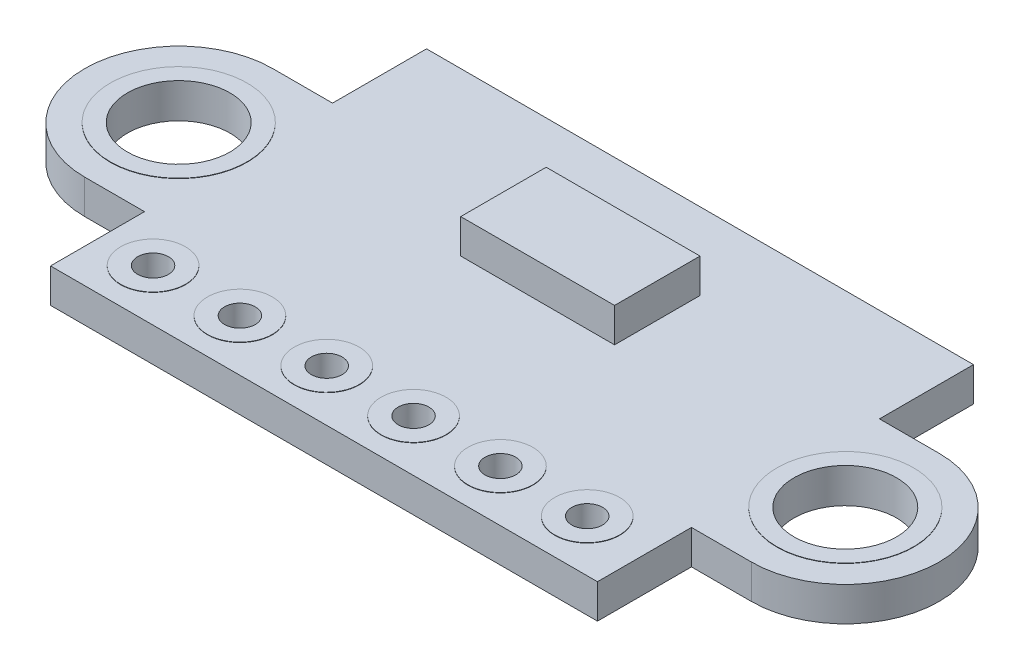
SolidWorks part; units mm, degrees
ref_plane "Front" through (0, 0, 0) normal (0, 0, 1) x (1, 0, 0)
ref_plane "Top" through (0, 0, 0) normal (0, 1, 0) x (1, 0, 0)
ref_plane "Right" through (0, 0, 0) normal (1, 0, 0) x (0, 0, -1)
sketch "Эскиз1" plane through (0, 0, 0) normal (0, 1, 0) x (1, 0, 0)
  line L0 (-38.6022, 0) -> (38.6022, 0) construction
  line L1 (8, -5.5) -> (-8, -5.5)
  line L2 (8, -5.5) -> (8, 5.5) construction
  line L3 (8, 5.5) -> (-8, 5.5)
  line L4 (-8, -5.5) -> (-8, 5.5) construction
  line L5 (8, -5.5) -> (-8, 5.5) construction
  line L6 (8, 5.5) -> (-8, -5.5) construction
  line L7 (-8, 5.5) -> (-8, 2.75)
  line L8 (0, -16.638) -> (0, 16.638) construction
  line L9 (-9.75, 2.75) -> (-8, 2.75)
  line L10 (-8, -5.5) -> (-8, -2.75)
  line L11 (-9.75, -2.75) -> (-8, -2.75)
  line L12 (9.75, -2.75) -> (8, -2.75)
  line L13 (8, -5.5) -> (8, -2.75)
  line L14 (8, 5.5) -> (8, 2.75)
  line L15 (9.75, 2.75) -> (8, 2.75)
  circle A0 centre (-9.75, 0) radius 1.5
  arc A1 (-9.75, 2.75) -> (-9.75, -2.75) centre (-9.75, 0) ccw
  circle A2 centre (9.75, 0) radius 1.5
  arc A3 (9.75, 2.75) -> (9.75, -2.75) centre (9.75, 0) cw
  circle A4 centre (-9.75, 0) radius 2
  circle A5 centre (9.75, 0) radius 2
  circle A6 centre (-6.5, -4) radius 0.45
  circle A7 centre (-6.5, -4) radius 0.95
  circle A8 centre (-3.96, -4) radius 0.95
  circle A9 centre (-3.96, -4) radius 0.45
  circle A10 centre (-1.42, -4) radius 0.95
  circle A11 centre (-1.42, -4) radius 0.45
  circle A12 centre (1.12, -4) radius 0.95
  circle A13 centre (1.12, -4) radius 0.45
  circle A14 centre (3.66, -4) radius 0.95
  circle A15 centre (3.66, -4) radius 0.45
  circle A16 centre (6.2, -4) radius 0.95
  circle A17 centre (6.2, -4) radius 0.45
  point P0 (0, 0)
  point P9 (0, 0)
  point P13 (0, 0)
  point P18 (-12.5, 0)
  point P25 (12.5, 0)
  dimension "D1" = 3
  dimension "D2" = 2.75
  dimension "D6" = 4
  dimension "D7" = 0.9
  dimension "D8" = 1.9
  dimension "D3" = 16
  dimension "D4" = 11
  dimension "D5" = 25
  dimension "D9" = 1.5
  dimension "D10" = 1.5
  dimension "D12" = 2.54
  dimension "D11" = 6
extrude "Бобышка-Вытянуть1" add sketch "Эскиз1" along normal blind 1 contours A0 | A2 | A6 | A9 | A11 | A13 | A15 | A17 | L7 L9 A1 L11 L10 L1 L13 L12 A3 L15 L14 L3 region at (-9.75, 0, 0) region at (9.75, 0, 0) region at (-6.5, 0, 4) region at (-3.96, 0, 4) region at (-1.42, 0, 4) region at (1.12, 0, 4) region at (3.66, 0, 4) region at (6.2, 0, 4)
extrude "Бобышка-Вытянуть2" add sketch "Эскиз1<3>" along normal blind 1.02 from offset 0.01 contours A4 A0 | A7 A6 | A8 A9 | A10 A11 | A12 A13 | A14 A15 | A16 A17 | A5 A2 region at (-11.6934, 0, 0) region at (7.8066, 0, 0) region at (-7.4231, 0, 4) region at (-4.8831, 0, 4) region at (-2.3431, 0, 4) region at (0.1969, 0, 4) region at (2.7369, 0, 4) region at (5.2769, 0, 4) offset against normal yes
sketch "Эскиз1<3>" plane through (0, 0, 0) normal (0, 1, 0) x (1, 0, 0) same geometry as "Эскиз1"
sketch "Эскиз2" plane through (0, 1, 0) normal (0, 1, 0) x (1, 0, 0)
  line L0 (8, 5.5) -> (-8, 5.5) construction
  line L1 (2.25, 0.75) -> (-2.25, 0.75)
  line L2 (2.25, 0.75) -> (2.25, 3.25)
  line L3 (2.25, 3.25) -> (-2.25, 3.25)
  line L4 (-2.25, 0.75) -> (-2.25, 3.25)
  line L5 (2.25, 0.75) -> (-2.25, 3.25) construction
  line L6 (2.25, 3.25) -> (-2.25, 0.75) construction
  point P0 (0, 2)
  dimension "D1" = 4.5
  dimension "D2" = 2.5
  dimension "D3" = 2.25
extrude "Бобышка-Вытянуть3" add sketch "Эскиз2" along normal blind 1
sketch "Эскиз3" plane through (0, 0, 0) normal (0, -1, 0) x (1, 0, 0)
  line L0 (8, -5.5) -> (-8, -5.5) construction
  line L1 (-6, 2.3) -> (-4.4, 2.3)
  line L2 (-6, 2.3) -> (-6, 1.45)
  line L3 (-6, 1.45) -> (-4.4, 1.45)
  line L4 (-4.4, 2.3) -> (-4.4, 1.45)
  line L5 (-5.2, 1.45) -> (-5.2, 2.3) construction
  line L6 (-6, 1.875) -> (-4.4, 1.875) construction
  line L7 (-7, -0.5) -> (-4, -0.5)
  line L8 (-7, -0.5) -> (-7, -2)
  line L9 (-7, -2) -> (-4, -2)
  line L10 (-4, -0.5) -> (-4, -2)
  line L11 (-5.5, -2) -> (-5.5, -0.5) construction
  line L12 (-7, -1.25) -> (-4, -1.25) construction
  line L13 (-3, -0.5) -> (-1.2, -0.5)
  line L14 (-3, -0.5) -> (-3, 2.5)
  line L15 (-3, 2.5) -> (-1.2, 2.5)
  line L16 (-1.2, -0.5) -> (-1.2, 2.5)
  line L17 (-2.1, 2.5) -> (-2.1, -0.5) construction
  line L18 (-3, 1) -> (-1.2, 1) construction
  line L19 (0.5, 1.5) -> (2.5, 1.5)
  line L20 (0.5, 1.5) -> (0.5, 0.3)
  line L21 (0.5, 0.3) -> (2.5, 0.3)
  line L22 (2.5, 1.5) -> (2.5, 0.3)
  line L23 (1.5, 0.3) -> (1.5, 1.5) construction
  line L24 (0.5, 0.9) -> (2.5, 0.9) construction
  line L25 (4.65, 0.1) -> (5.5, 0.1)
  line L26 (4.65, 0.1) -> (4.65, -1.5)
  line L27 (4.65, -1.5) -> (5.5, -1.5)
  line L28 (5.5, 0.1) -> (5.5, -1.5)
  line L29 (5.075, -1.5) -> (5.075, 0.1) construction
  line L30 (4.65, -0.7) -> (5.5, -0.7) construction
  line L31 (6.15, 0.1) -> (7, 0.1)
  line L32 (6.15, 0.1) -> (6.15, -1.5)
  line L33 (6.15, -1.5) -> (7, -1.5)
  line L34 (7, 0.1) -> (7, -1.5)
  line L35 (6.575, -1.5) -> (6.575, 0.1) construction
  line L36 (6.15, -0.7) -> (7, -0.7) construction
  line L37 (-2.115, -2.9) -> (-1.265, -2.9)
  line L38 (-2.115, -2.9) -> (-2.115, -4.5)
  line L39 (-2.115, -4.5) -> (-1.265, -4.5)
  line L40 (-1.265, -2.9) -> (-1.265, -4.5)
  line L41 (-1.69, -4.5) -> (-1.69, -2.9) construction
  line L42 (-2.115, -3.7) -> (-1.265, -3.7) construction
  line L43 (-0.425, -2.9) -> (0.425, -2.9)
  line L44 (-0.425, -2.9) -> (-0.425, -4.5)
  line L45 (-0.425, -4.5) -> (0.425, -4.5)
  line L46 (0.425, -2.9) -> (0.425, -4.5)
  line L47 (0, -4.5) -> (0, -2.9) construction
  line L48 (-0.425, -3.7) -> (0.425, -3.7) construction
  line L49 (1.265, -2.9) -> (2.115, -2.9)
  line L50 (1.265, -2.9) -> (1.265, -4.5)
  line L51 (1.265, -4.5) -> (2.115, -4.5)
  line L52 (2.115, -2.9) -> (2.115, -4.5)
  line L53 (1.69, -4.5) -> (1.69, -2.9) construction
  line L54 (1.265, -3.7) -> (2.115, -3.7) construction
  line L55 (-8, -5.5) -> (-8, -2.75) construction
  line L56 (-8, 5.5) -> (-8, 2.75) construction
  line L57 (8, 5.5) -> (-8, 5.5) construction
  line L58 (8, -5.5) -> (8, -2.75) construction
  line L59 (8, 5.5) -> (8, 2.75) construction
  point P88 (5.075, -0.7)
  point P96 (-5.2, 1.875)
  point P102 (-1.69, -3.7)
  point P123 (0, -3.7)
  point P129 (-5.5, -1.25)
  point P158 (-2.1, 1)
  point P160 (6.575, -0.7)
  point P167 (1.69, -3.7)
  point P179 (1.5, 0.9)
  dimension "D1" = 1.6
  dimension "D2" = 0.85
  dimension "D3" = 1.69
  dimension "D4" = 1.69
  dimension "D5" = 1
  dimension "D6" = 3
  dimension "D7" = 1.5
  dimension "D8" = 3.5
  dimension "D9" = 1
  dimension "D10" = 1.8
  dimension "D11" = 3
  dimension "D12" = 2
  dimension "D13" = 3.2
  dimension "D14" = 1.5
  dimension "D15" = 4
  dimension "D16" = 1
  dimension "D17" = 1.2
  dimension "D18" = 2
  dimension "D19" = 4
  dimension "D20" = 5.5
  dimension "D21" = 3
  dimension "D22" = 5
extrude "Бобышка-Вытянуть4" add sketch "Эскиз3" along normal blind 0.8 contours L4 L1 L2 L3 | L40 L37 L38 L39 | L46 L43 L44 L45 | L52 L49 L50 L51 region at (-5.2, 0, 1.875) region at (-1.69, 0, -3.7) region at (0, 0, -3.7) region at (1.69, 0, -3.7)
extrude "Бобышка-Вытянуть5" add sketch "Эскиз3<3>" along normal blind 0.5 contours L34 L31 L32 L33 | L28 L25 L26 L27 | L13 L16 L15 L14 region at (-2.1, 0, 1) region at (5.075, 0, -0.7) region at (6.575, 0, -0.7)
sketch "Эскиз3<3>" plane through (0, 0, 0) normal (0, -1, 0) x (1, 0, 0) same geometry as "Эскиз3"
extrude "Бобышка-Вытянуть6" add sketch "Эскиз3<4>" along normal blind 1 contours L10 L7 L8 L9 | L22 L19 L20 L21 region at (-5.5, 0, -1.25) region at (1.5, 0, 0.9)
sketch "Эскиз3<4>" plane through (0, 0, 0) normal (0, -1, 0) x (1, 0, 0) same geometry as "Эскиз3"
equation "\"D3@Эскиз2\"=11-8.75"
